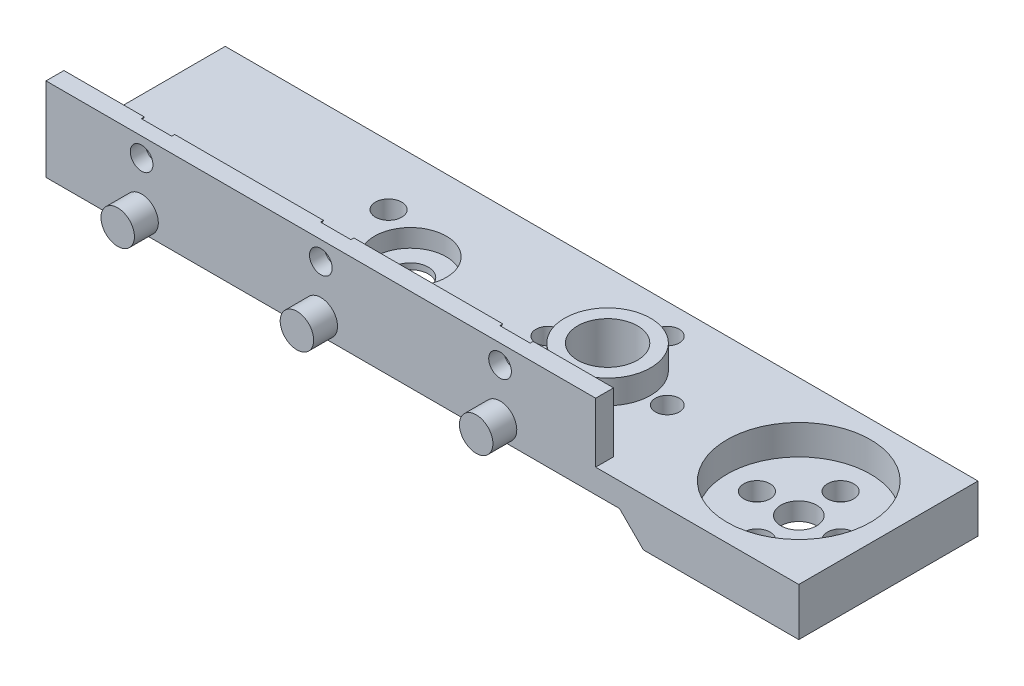
SolidWorks part; units mm, degrees
note: The reader was unsure of these and kept them because the rebuilt part matched: shared geometry of "草图2<3>", "草图1<3>", "草图1<4>", "草图1<5>".
ref_plane "前视基准面" through (0, 0, 0) normal (0, 0, 1) x (1, 0, 0)
ref_plane "上视基准面" through (0, 0, 0) normal (0, 1, 0) x (1, 0, 0)
ref_plane "右视基准面" through (0, 0, 0) normal (1, 0, 0) x (0, 0, -1)
other "Configuration Table"
sketch "草图1" plane through (0, 0, 0) normal (0, 1, 0) x (1, 0, 0)
  line L0 (-31.5, 7.5) -> (31.5, 7.5)
  line L1 (31.5, 7.5) -> (31.5, -7.5)
  line L2 (31.5, -7.5) -> (-31.5, -7.5)
  line L3 (-31.5, -7.5) -> (-31.5, 7.5)
  line L4 (-31.5, 0) -> (31.5, 0) construction
  line L5 (-12.8301, -2.5) -> (-4.1699, 2.5) construction
  line L6 (-13.3083, -5.95) -> (-3.6917, -5.95) construction
  line L7 (-13.3083, 5.95) -> (-3.6917, 5.95) construction
  line L8 (-8.5, 7.5) -> (-8.5, -7.5) construction
  line L9 (8, 0) -> (8, 4.5778) construction
  line L11 (31.5, 7.5) -> (16.5, 7.5)
  line L12 (31.5, 7.5) -> (31.5, -7.5)
  line L13 (31.5, -7.5) -> (16.5, -7.5)
  line L14 (16.5, 7.5) -> (16.5, -7.5)
  circle A0 centre (-8.5, 0) radius 1.5
  circle A1 centre (-4.1699, 2.5) radius 1.1
  circle A3 centre (-12.8301, -2.5) radius 1.1
  arc A4 (-13.3083, 5.95) -> (-13.3083, -5.95) centre (-8.5, 0) ccw construction
  circle A5 centre (8, 0) radius 2.5
  arc A6 (-3.6917, -5.95) -> (-3.6917, 5.95) centre (-8.5, 0) ccw construction
  circle A7 centre (24, 0) radius 1.5
  circle A8 centre (24, 0) radius 3.5 construction
  circle A9 centre (27.5, 0) radius 1.1
  circle A10 centre (24, -3.5) radius 1.1
  circle A11 centre (20.5, 0) radius 1.1
  circle A12 centre (24, 3.5) radius 1.1
  circle A13 centre (-12.8301, 2.5) radius 1.1
  circle A14 centre (-4.1699, -2.5) radius 1.1
  circle A15 centre (13, 0) radius 1
  circle A18 centre (3, 0) radius 1
  circle A19 centre (8, 5) radius 1
  circle A20 centre (8, -5) radius 1 [skipped]
  circle A21 centre (24, 0) radius 6
  point P5 (0, 7.5)
  point P7 (-31.5, 0)
  dimension "D3" = 3
  dimension "D6" = 2.2
  dimension "D9" = 15.3
  dimension "D12" = 5
  dimension "D14" = 3
  dimension "D15" = 7
  dimension "D16" = 2.2
  dimension "D18" = 2
  dimension "D22" = 12
  dimension "D1" = 63
  dimension "D2" = 15
  dimension "D4" = 23
  dimension "D7" = 30
  dimension "D8" = 10
  dimension "D10" = 11.9
  dimension "D11" = 16.5
  dimension "D13" = 16
  dimension "D19" = 5
  dimension "D21" = 15
  dimension "D5" = 2
  dimension "D17" = 4
  dimension "D20" = 4
extrude "凸台-拉伸1" add sketch "草图1" along normal blind 2 contours L3 L2 L1 L0 A13 A12 A11 A10 A9 A7 A5 A3 A1 A0 A14 | A3 | A1
sketch "草图2" plane through (0, 0, 7.5) normal (0, 0, 1) x (1, 0, 0)
  line L0 (-31, 1.4) -> (31, 1.4) construction
  line L1 (-31.5, 2) -> (-31.5, 0) construction
  line L3 (16.5, 0) -> (-31.5, 0) construction
  circle A0 centre (-23.5, 1.4) radius 1.4
  circle A1 centre (-8.5, 1.4) radius 1.4
  circle A2 centre (6.5, 1.4) radius 1.4
  circle A3 centre (-23.5, 5.4) radius 0.95
  circle A4 centre (-8.5, 5.4) radius 0.95
  circle A5 centre (6.5, 5.4) radius 0.95
  line M10 (16.5, 2) -> (-31.5, 2)
  dimension "D1" = 2.8
  dimension "D2" = 2.8
  dimension "D3" = 2.8
  dimension "D8" = 1.9
  dimension "D4" = 15
  dimension "D5" = 15
  dimension "D6" = 8
  dimension "D7" = 1.4
  dimension "D9" = 4
  dimension "D10" = 3
extrude "凸台-拉伸2" add sketch "草图2" along normal blind 2 contours L0 A0 | A0 L0 M10 | A0 M10 | L0 A1 | A1 L0 M10 | A1 M10 | L0 A2 | A2 L0 M10 | A2 M10
sketch "草图3" plane through (0, 2, 0) normal (0, 1, 0) x (1, 0, 0)
  text T0 "R" font "Microsoft YaHei UI" height 3.5
sketch "草图4" plane through (0, 2, 0) normal (0, 1, 0) x (1, 0, 0)
  circle A0 centre (-8.5, 0) radius 3
  dimension "D1" = 6
extrude "切除-拉伸1" cut sketch "草图4" against normal blind 1.5
sketch "草图5" plane through (0, 2, 0) normal (0, 1, 0) x (1, 0, 0)
  line L1 (-31.5, -7.5) -> (14.5, -7.5)
  line L2 (-31.5, -7.5) -> (-31.5, -6)
  line L3 (-31.5, -6) -> (14.5, -6)
  line L4 (14.5, -7.5) -> (14.5, -6)
  dimension "D1" = 1.5
  dimension "D2" = 46
extrude "凸台-拉伸3" add sketch "草图5" along normal blind 5
extrude "切除-拉伸2" cut sketch "草图2<3>" against normal blind 6 contours A3 | A4 | A5
sketch "草图2<3>" plane through (0, 0, 7.5) normal (0, 0, 1) x (1, 0, 0) same geometry as "草图2"
sketch "草图7" plane through (0, 0, 6) normal (0, 0, -1) x (-1, 0, 0)
  line L0 (-7.597, 3.5) -> (-5.403, 3.5)
  line L1 (-5.403, 3.5) -> (-4.3061, 5.4)
  line L2 (-4.3061, 5.4) -> (-5.403, 7.3)
  line L3 (-5.403, 7.3) -> (-7.597, 7.3)
  line L4 (-7.597, 7.3) -> (-8.6939, 5.4)
  line L5 (-8.6939, 5.4) -> (-7.597, 3.5)
  line L6 (-7.597, 7.3) -> (-5.403, 3.5) construction
  line L7 (-5.403, 7.3) -> (-7.597, 3.5) construction
  line L8 (6.3061, 5.4) -> (7.403, 3.5)
  line L9 (7.403, 3.5) -> (9.597, 3.5)
  line L10 (9.597, 3.5) -> (10.6939, 5.4)
  line L11 (10.6939, 5.4) -> (9.597, 7.3)
  line L12 (9.597, 7.3) -> (7.403, 7.3)
  line L13 (7.403, 7.3) -> (6.3061, 5.4)
  line L14 (21.3061, 5.4) -> (22.403, 3.5)
  line L15 (22.403, 3.5) -> (24.597, 3.5)
  line L16 (24.597, 3.5) -> (25.6939, 5.4)
  line L17 (25.6939, 5.4) -> (24.597, 7.3)
  line L18 (24.597, 7.3) -> (22.403, 7.3)
  line L19 (22.403, 7.3) -> (21.3061, 5.4)
  line L20 (7.403, 7.3) -> (9.597, 3.5) construction
  line L21 (9.597, 7.3) -> (7.403, 3.5) construction
  circle A0 centre (-6.5, 5.4) radius 0.95
  circle A1 centre (-6.5, 5.4) radius 0.95 construction
  circle A2 centre (8.5, 5.4) radius 0.95
  circle A3 centre (8.5, 5.4) radius 0.95 construction
  point P11 (-6.5, 5.4)
  point P29 (8.5, 5.4)
  dimension "D1" = 3.8
  dimension "D2" = 3.8
  dimension "D3" = 3.8
  dimension "D4" = 120
  dimension "D5" = 120
  dimension "D6" = 120
  dimension "D7" = 3
extrude "切除-拉伸3" cut sketch "草图7" against normal blind 0.25
extrude "凸台-拉伸4" add sketch "草图1<3>" along normal blind 2 contours L0 L14 L2 L1 A21 | A21 A7 A9 A10 A11 A12
sketch "草图1<3>" plane through (0, 0, 0) normal (0, 1, 0) x (1, 0, 0) same geometry as "草图1"
extrude "凸台-拉伸5" add sketch "草图1<4>" against normal blind 2 contours L0 L14 L2 L1 A21 | A21 A7 A9 A10 A11 A12
sketch "草图1<4>" plane through (0, 0, 0) normal (0, 1, 0) x (1, 0, 0) same geometry as "草图1"
extrude "切除-拉伸4" cut sketch "草图1<5>" along normal up to surface (2 mm away) and the other way blind 0.5 contours A21 up to face at (-8.5, 2, 3)
sketch "草图1<5>" plane through (0, 0, 0) normal (0, 1, 0) x (1, 0, 0) same geometry as "草图1"
sketch "草图8" plane through (0, 0, -7.5) normal (0, 0, -1) x (-1, 0, 0)
  line L0 (-16.5, 0) -> (-18.5, -2)
  line L1 (-16.5, -2) -> (-31.5, -2) construction
  line L2 (-18.5, -2) -> (-16.5, -2)
  line L3 (-16.5, -2) -> (-16.5, 0)
  dimension "D1" = 45
extrude "切除-拉伸5" cut sketch "草图8" against normal up to surface (15 mm away) up to face at (-22.55, 5.4, 7.5)
sketch "草图9" plane through (0, 2, 0) normal (0, 1, 0) x (1, 0, 0)
  circle A0 centre (8, 0) radius 2.5
  circle A1 centre (8, 0) radius 3.6
  circle A2 centre (8, 0) radius 2.5 construction
  dimension "D1" = 7.2
extrude "凸台-拉伸6" add sketch "草图9" along normal blind 2
